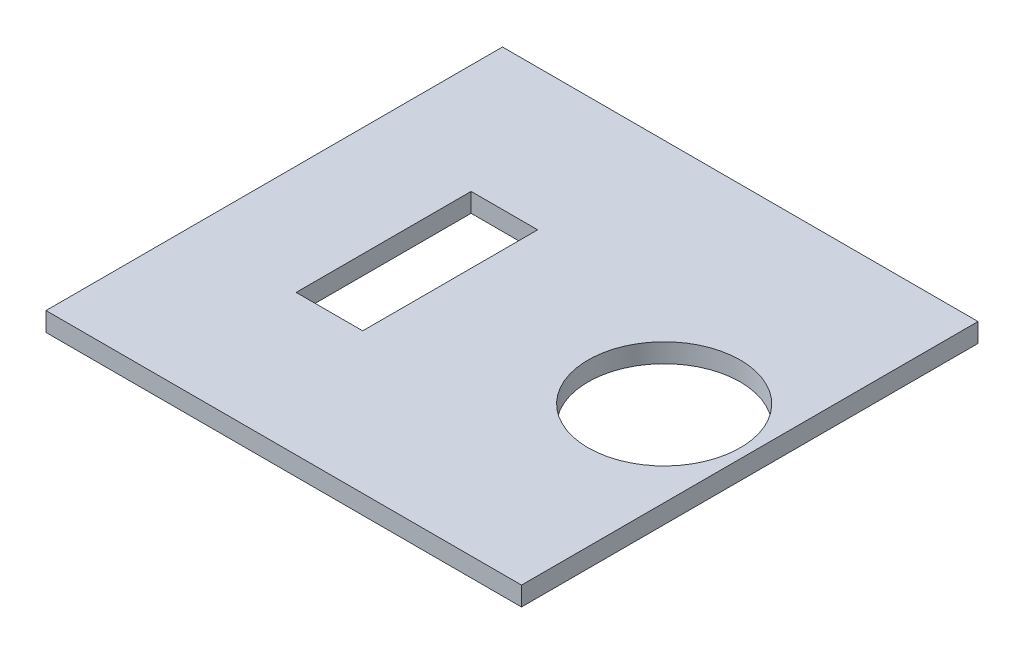
SolidWorks part; units mm, degrees
ref_plane "Front Plane" through (0, 0, 0) normal (0, 0, 1) x (1, 0, 0)
ref_plane "Top Plane" through (0, 0, 0) normal (0, 1, 0) x (1, 0, 0)
ref_plane "Right Plane" through (0, 0, 0) normal (1, 0, 0) x (0, 0, -1)
sketch "Sketch1" plane through (0, 0, 0) normal (0, 1, 0) x (1, 0, 0)
  line L1 (-12.5, -12) -> (12.5, -12)
  line L2 (-12.5, -12) -> (-12.5, 12)
  line L3 (-12.5, 12) -> (12.5, 12)
  line L4 (12.5, -12) -> (12.5, 12)
  line L5 (-12.5, -12) -> (12.5, 12) construction
  line L6 (-12.5, 12) -> (12.5, -12) construction
  line L7 (-6.75, -4.6) -> (-3.25, -4.6)
  line L8 (-6.75, -4.6) -> (-6.75, 4.6)
  line L9 (-6.75, 4.6) -> (-3.25, 4.6)
  line L10 (-3.25, -4.6) -> (-3.25, 4.6)
  line L11 (-6.75, -4.6) -> (-3.25, 4.6) construction
  line L12 (-6.75, 4.6) -> (-3.25, -4.6) construction
  circle A0 centre (8, 0) radius 4
  point P0 (0, 0)
  point P6 (-5, 0)
  dimension "D3" = 8
  dimension "D1" = 25
  dimension "D2" = 24
  dimension "D4" = 9.2
  dimension "D5" = 3.5
  dimension "D6" = 12
  dimension "D7" = 12
  dimension "D8" = 7.5
  dimension "D9" = 13
extrude "Boss-Extrude1" add sketch "Sketch1" along normal blind 1
